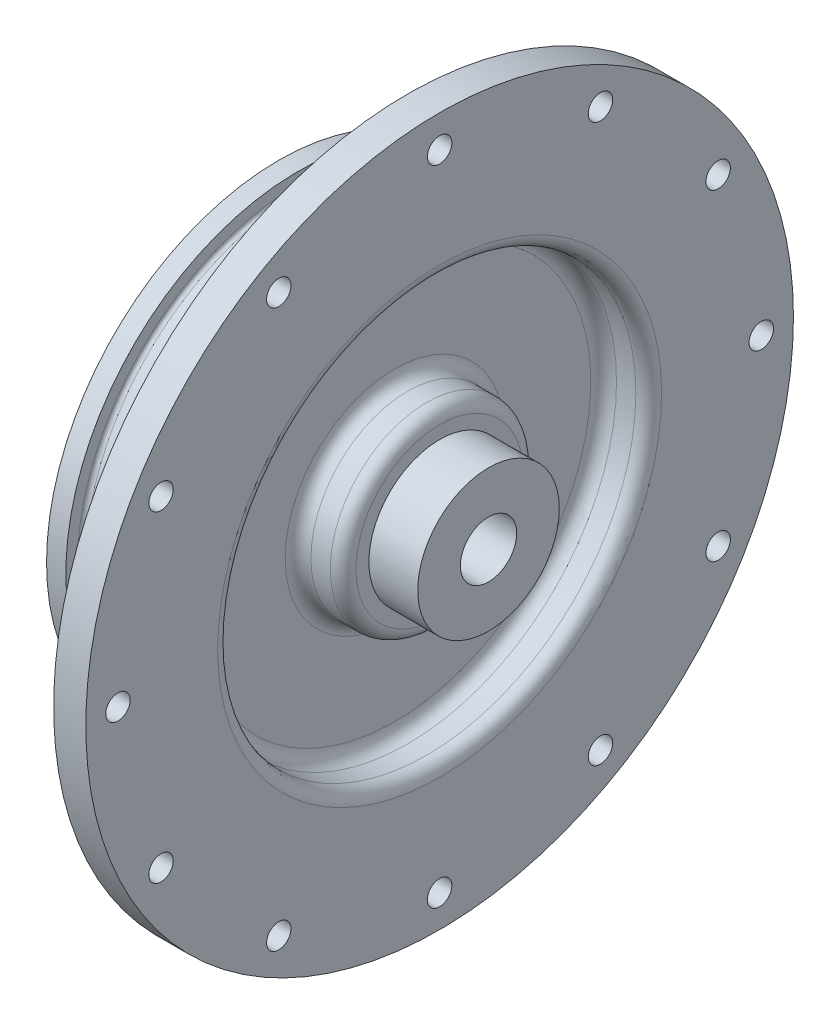
SolidWorks part; units mm, degrees
material "7075-T6 (SN)"
ref_plane "Front Plane" through (0, 0, 0) normal (0, 0, 1) x (1, 0, 0)
ref_plane "Top Plane" through (0, 0, 0) normal (0, 1, 0) x (1, 0, 0)
ref_plane "Right Plane" through (0, 0, 0) normal (1, 0, 0) x (0, 0, -1)
sketch "Sketch1" plane through (0, 0, 0) normal (1, 0, 0) x (0, 0, -1)
  circle A0 centre (0, 0) radius 69.85
  dimension "D1" = 139.7
extrude "Boss-Extrude1" add sketch "Sketch1" along normal blind 6.35
sketch "Sketch2" plane through (0, 0, 0) normal (-1, 0, 0) x (0, 0, 1)
  circle A0 centre (0, 0) radius 45.847
  dimension "D1" = 91.694
extrude "Boss-Extrude2" add sketch "Sketch2" along normal blind 25.4
sketch "Sketch10" plane through (0, 0, 0) normal (0, 1, 0) x (1, 0, 0)
  line L0 (0, 0) -> (-53.2238, 0) construction
  line L1 (-26.2636, 0) -> (26.2636, 0) construction
  line L2 (0, 0) -> (0, 64.5447) construction
  line L3 (0, -62.865) -> (0, 62.865) construction
ref_plane "Plane1" through (0, 0, -45.847) normal (0, 0, -1) x (-1, 0, 0)
sketch "Sketch11" plane through (0, 0, -45.847) normal (0, 0, -1) x (-1, 0, 0)
  line L0 (0, 0) -> (53.2238, 0) construction
  line L1 (0, -45.847) -> (0, 45.847) construction
  circle A0 centre (7.62, 0) radius 1.8986
  dimension "D2" = 3.7973
  dimension "D1" = 7.62
extrude "Cut-Extrude3" cut sketch "Sketch11" against normal blind 10.16
pattern_circular "CirPattern1" count 12 over 360 about axis through (0, 0, 0) along (-1, 0, 0) of "Cut-Extrude3" reverse direction yes
sketch "Sketch15" plane through (6.35, 0, 0) normal (1, 0, 0) x (0, 0, -1)
  circle A0 centre (0, 0) radius 5.5562
  dimension "D1" = 11.1125
extrude "Cut-Extrude4" cut sketch "Sketch15" against normal through all both and the other way through all
sketch "Sketch16" plane through (0, 0, 0) normal (0, 0, 1) x (1, 0, 0)
  line L0 (-9.5186, 45.847) -> (-25.4, 45.847) construction
  line L1 (-21.59, 45.847) -> (-14.4018, 45.847)
  line L2 (-21.59, 45.847) -> (-21.59, 43.6245)
  line L3 (-20.828, 42.8625) -> (-15.1638, 42.8625)
  line L4 (-14.4018, 45.847) -> (-14.4018, 43.6245)
  line L5 (0, 0) -> (-53.2238, 0) construction
  line L6 (-25.4, 45.847) -> (-25.4, -45.847) construction
  arc A0 (-14.4018, 43.6245) -> (-15.1638, 42.8625) centre (-15.1638, 43.6245) cw
  arc A1 (-20.828, 42.8625) -> (-21.59, 43.6245) centre (-20.828, 43.6245) cw
  point P8 (-26.6119, 0)
  point P13 (-14.4018, 42.8625)
  point P16 (-21.59, 42.8625)
  dimension "D4" = 0.762
  dimension "D1" = 42.8625
  dimension "D2" = 3.81
  dimension "D3" = 7.1882
revolve "Cut-Revolve1" cut sketch "Sketch16" angle 360 about L0
sketch "Sketch17" plane through (6.35, 0, 0) normal (1, 0, 0) x (0, 0, -1)
  circle A0 centre (0, 0) radius 13.97
  circle A1 centre (0, 0) radius 5.5562
  dimension "D1" = 27.94
  dimension "D2" = 11.1125
extrude "Boss-Extrude3" add sketch "Sketch17" along normal blind 9.652
cosmetic thread "Cosmetic Thread1" parameters "D2"=23.1953
sketch "Sketch18" plane through (0, 0, 0) normal (0, 0, 1) x (1, 0, 0)
  line L0 (6.35, -69.85) -> (6.35, 69.85) construction
  line L1 (6.35, 41.275) -> (-2.54, 41.275)
  line L2 (6.35, 41.275) -> (6.35, 19.05)
  line L3 (6.35, 19.05) -> (-2.54, 19.05)
  line L4 (-2.54, 41.275) -> (-2.54, 19.05)
  line L5 (0, 0) -> (-53.2238, 0) construction
  dimension "D1" = 8.89
  dimension "D2" = 19.05
  dimension "D3" = 41.275
revolve "Cut-Revolve2" cut sketch "Sketch18" angle 360 about L0
fillet "Fillet1" radius 2.54 4 edges at (6.35, 0, -41.275) (-2.54, 0, -41.275) (-2.54, 0, -19.05) (6.35, 0, -19.05)
sketch "Sketch19" plane through (6.35, 0, 0) normal (1, 0, 0) x (0, 0, -1)
  line L0 (0, 0) -> (0, 63.5) construction
  circle A0 centre (0, 0) radius 57.15 construction
  circle A1 centre (0, 0) radius 63.5 construction
  circle A2 centre (0, 63.5) radius 2.413
  circle A3 centre (31.75, 54.9926) radius 2.413
  circle A4 centre (54.9926, 31.75) radius 2.413
  circle A5 centre (63.5, 0) radius 2.413
  circle A6 centre (54.9926, -31.75) radius 2.413
  circle A7 centre (31.75, -54.9926) radius 2.413
  circle A8 centre (0, -63.5) radius 2.413
  circle A9 centre (-31.75, -54.9926) radius 2.413
  circle A10 centre (-54.9926, -31.75) radius 2.413
  circle A11 centre (-63.5, 0) radius 2.413
  circle A12 centre (-54.9926, 31.75) radius 2.413
  circle A13 centre (-31.75, 54.9926) radius 2.413
  point P30 (0, 0)
  dimension "D1" = 114.3
  dimension "D2" = 127
  dimension "D3" = 4.826
  dimension "D4" = 12
extrude "Cut-Extrude5" cut sketch "Sketch19" against normal through all
